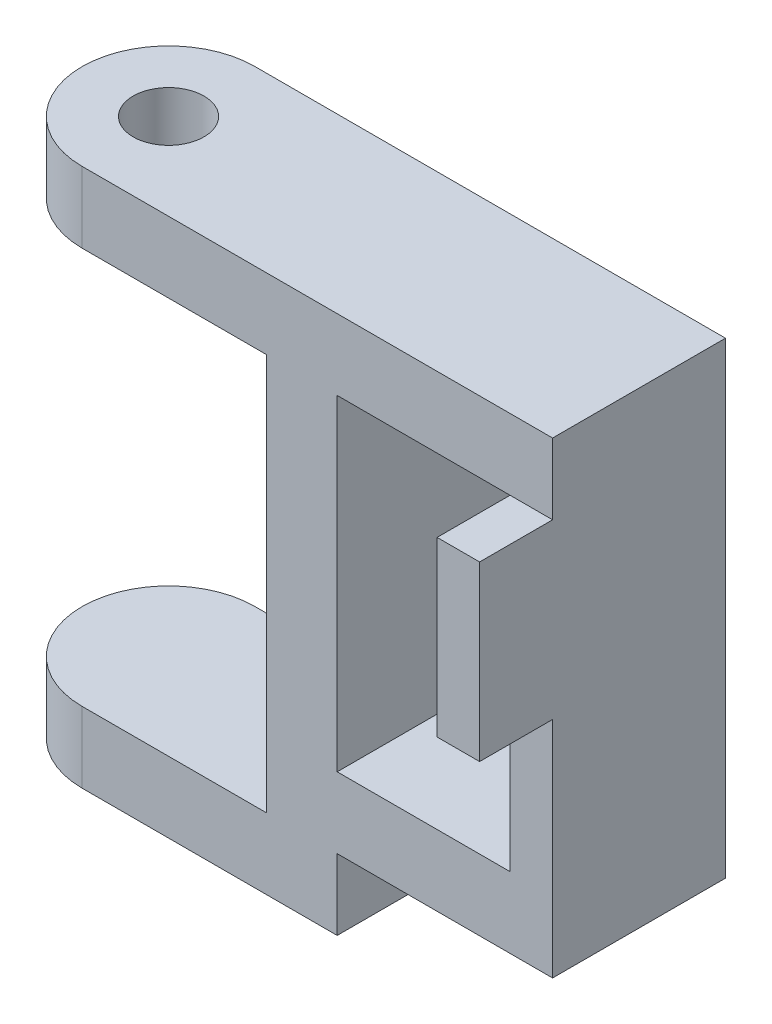
SolidWorks part; units mm, degrees
ref_plane "Front Plane" through (0, 0, 0) normal (0, 0, 1) x (1, 0, 0)
ref_plane "Top Plane" through (0, 0, 0) normal (0, 1, 0) x (1, 0, 0)
ref_plane "Right Plane" through (0, 0, 0) normal (1, 0, 0) x (0, 0, -1)
sketch "Sketch3" plane through (0, 0, 0) normal (0, 0, 1) x (1, 0, 0)
  line L0 (-40.4079, 21.4132) -> (-21.3079, 21.4132)
  line L1 (-21.3079, 21.4132) -> (-21.3079, -6.5868)
  line L2 (-21.3079, -6.5868) -> (-40.4079, -6.5868)
  line L3 (-40.4079, 26.4132) -> (-16.3079, 26.4132)
  line L4 (-16.3079, 26.4132) -> (-16.3079, -11.5868)
  line L5 (-16.3079, -11.5868) -> (-40.4079, -11.5868)
  line L6 (-40.4079, 26.4132) -> (-40.4079, 21.4132)
  line L7 (-40.4079, -6.5868) -> (-40.4079, -11.5868)
  dimension "D1" = 19.1
  dimension "D2" = 28
  dimension "D3" = 5
extrude "Boss-Extrude1" add sketch "Sketch3" along normal blind 12.2
sketch "Sketch4" plane through (0, 26.4132, 0) normal (0, 1, 0) x (1, 0, 0)
  line L0 (-40.4079, -6.1) -> (-34.3079, -6.1) construction
  line L1 (-40.4079, -12.2) -> (-40.4079, 0) construction
  line L4 (-16.3079, -12.2) -> (-40.4079, -12.2) construction
  line L5 (-16.3079, 0) -> (-40.4079, 0) construction
  arc A0 (-31.3079, -12.2) -> (-31.3079, 0) centre (-34.3079, -6.1) cw
  circle A1 centre (-34.3079, -6.1) radius 2.5
  dimension "D2" = 5
  dimension "D1" = 6.1
extrude "Cut-Extrude1" cut sketch "Sketch4" against normal blind 5 contours A1
sketch "Sketch5" plane through (0, 26.4132, 0) normal (0, 1, 0) x (1, 0, 0)
  line L0 (-40.4079, -6.1) -> (-34.3079, -6.1) construction
  line L1 (-40.4079, -12.2) -> (-40.4079, 0) construction
  line L2 (-34.3079, -6.1) -> (-34.3079, 0) construction
  line L3 (-16.3079, 0) -> (-40.4079, 0) construction
  line L4 (-34.3079, 0) -> (-34.3079, -12.2) construction
  line L5 (-16.3079, -12.2) -> (-40.4079, -12.2) construction
  arc A0 (-34.3079, -12.2) -> (-34.3079, 0) centre (-34.3079, -6.1) cw
  dimension "D1" = 6.1
extrude "Cut-Extrude2" cut sketch "Sketch5" against normal through all and the other way through all
sketch "Sketch6" plane through (0, -11.5868, 0) normal (0, -1, 0) x (1, 0, 0)
  line L0 (-34.3079, 12.2) -> (-34.3079, 6.1) construction
  circle A0 centre (-34.3079, 6.1) radius 2
  dimension "D2" = 4
  dimension "D1" = 6.1
extrude "Boss-Extrude2" add sketch "Sketch6" along normal blind 3 contours A0
sketch "Sketch7" plane through (-16.3079, 0, 0) normal (1, 0, 0) x (0, 0, -1)
  line L0 (-12.2, -11.5868) -> (-12.2, 26.4132) construction
  line L2 (0, -11.5868) -> (0, 26.4132) construction
  line L3 (-12.2, 26.4132) -> (0, 26.4132)
  line L4 (-12.2, 26.4132) -> (-12.2, 21.4141)
  line L5 (-12.2, 21.4141) -> (0, 21.4141)
  line L6 (0, 26.4132) -> (0, 21.4141)
  line L7 (-12.2, -6.5868) -> (0, -6.5868)
  line L8 (-12.2, -6.5868) -> (-12.2, -1.5868)
  line L9 (-12.2, -1.5868) -> (0, -1.5868)
  line L10 (0, -6.5868) -> (0, -1.5868)
  point P0 (-12.2, -6.5868)
  dimension "D1" = 4.9991
  dimension "D2" = 5
  dimension "D3" = 5
extrude "Boss-Extrude3" add sketch "Sketch7" along normal blind 15.2
sketch "Sketch9" plane through (0, 21.4141, 0) normal (0, -1, 0) x (1, 0, 0)
  line L0 (-1.1079, 12.2) -> (-16.3079, 12.2) construction
  line L1 (-1.1079, 0) -> (-4.1079, 0)
  line L2 (-1.1079, 0) -> (-1.1079, 12.2)
  line L3 (-1.1079, 12.2) -> (-4.1079, 12.2)
  line L4 (-4.1079, 0) -> (-4.1079, 12.2)
  dimension "D1" = 3
extrude "Boss-Extrude5" add sketch "Sketch9" along normal up to next contours L2 L1 L4 L3
sketch "Sketch10" plane through (0, 0, 12.2) normal (0, 0, 1) x (1, 0, 0)
  line L0 (-1.1079, 26.4132) -> (-1.1079, -6.5868) construction
  line L1 (-4.1079, 21.4141) -> (-1.1079, 21.4141)
  line L2 (-4.1079, 21.4141) -> (-4.1079, 9.2141)
  line L3 (-4.1079, 9.2141) -> (-1.1079, 9.2141)
  line L4 (-1.1079, 21.4141) -> (-1.1079, 9.2141)
  dimension "D1" = 12.2
extrude "Boss-Extrude6" add sketch "Sketch10" along normal blind 5.15
